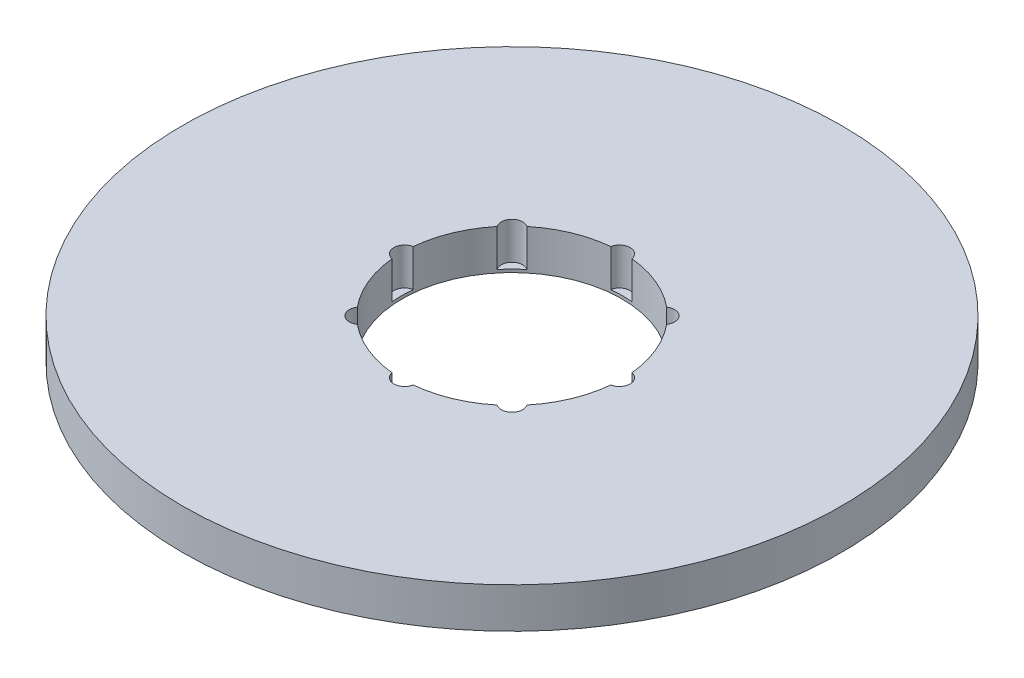
SolidWorks part; units mm, degrees
ref_plane "Front Plane" through (0, 0, 0) normal (0, 0, 1) x (1, 0, 0)
ref_plane "Top Plane" through (0, 0, 0) normal (0, 1, 0) x (1, 0, 0)
ref_plane "Right Plane" through (0, 0, 0) normal (1, 0, 0) x (0, 0, -1)
sketch "Sketch1" plane through (0, 0, 0) normal (0, 1, 0) x (1, 0, 0)
  circle A0 centre (0, 0) radius 90
  dimension "FLANGE_OD" = 180
extrude "Boss-Extrude1" add sketch "Sketch1" along normal blind 11
sketch "Sketch2" plane through (0, 0, 0) normal (0, 1, 0) x (1, 0, 0)
  circle A0 centre (0, 0) radius 30
  dimension "BORE_D" = 60
extrude "Cut-Extrude1" cut sketch "Sketch2" along normal through all
sketch "Sketch3" plane through (0, 11, 0) normal (0, 1, 0) x (1, 0, 0)
  circle A0 centre (0, 0) radius 29.3369 construction
  circle A1 centre (-29.3369, 0) radius 2.9269
  dimension "BOLT_D" = 5.8539
  dimension "BOLT_PCD" = 58.6738
extrude "Cut-Extrude2" cut sketch "Sketch3" against normal blind 10.1731
pattern_circular "CirPattern1" count 8 over 360 about axis through (0, 0, 0) along (0, 1, 0) of "Cut-Extrude2"
